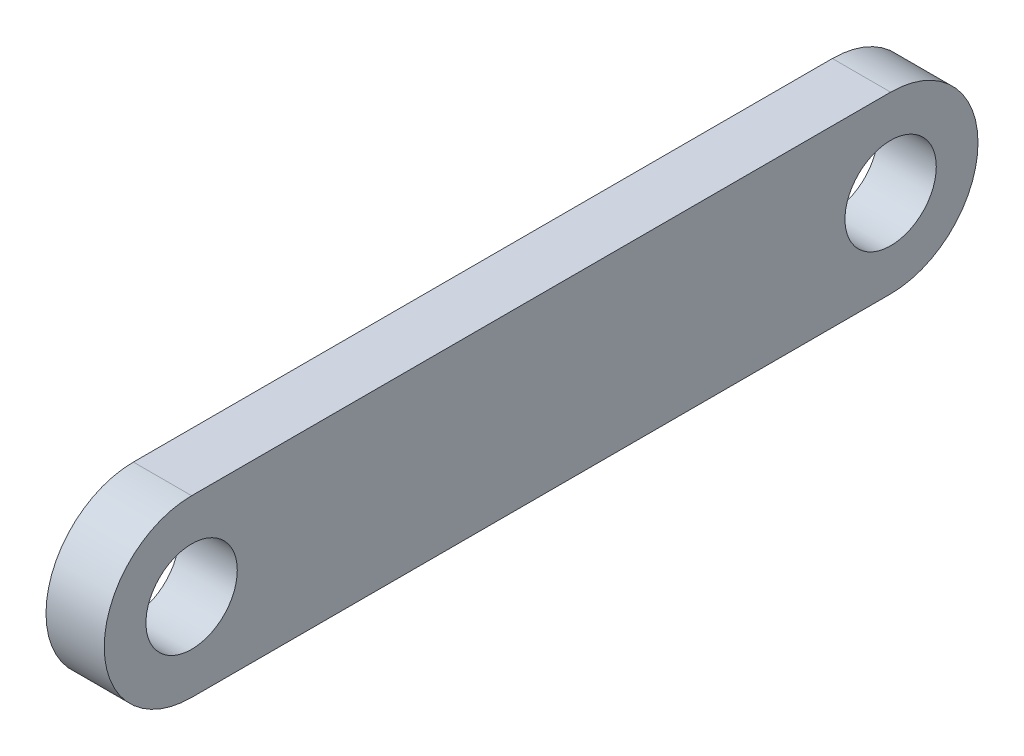
SolidWorks part; units mm, degrees
material "PET"
ref_plane "Front Plane" through (0, 0, 0) normal (0, 0, 1) x (1, 0, 0)
ref_plane "Top Plane" through (0, 0, 0) normal (0, 1, 0) x (1, 0, 0)
ref_plane "Right Plane" through (0, 0, 0) normal (1, 0, 0) x (0, 0, -1)
sketch "Sketch1" plane through (0, 0, 0) normal (1, 0, 0) x (0, 0, -1)
  line L0 (0, 0) -> (38.1, 0) construction
  line L1 (0, 4.7625) -> (38.1, 4.7625)
  line L2 (0, -4.7625) -> (38.1, -4.7625)
  arc A0 (0, 4.7625) -> (0, -4.7625) centre (0, 0) ccw
  arc A1 (38.1, -4.7625) -> (38.1, 4.7625) centre (38.1, 0) ccw
  circle A2 centre (38.1, 0) radius 2.4892
  circle A3 centre (0, 0) radius 2.4892
  point P3 (19.05, 0)
  dimension "D1" = 4.7625
  dimension "D3" = 4.9784
  dimension "D2" = 38.1
extrude "Boss-Extrude1" add sketch "Sketch1" along normal mid plane 3.175
